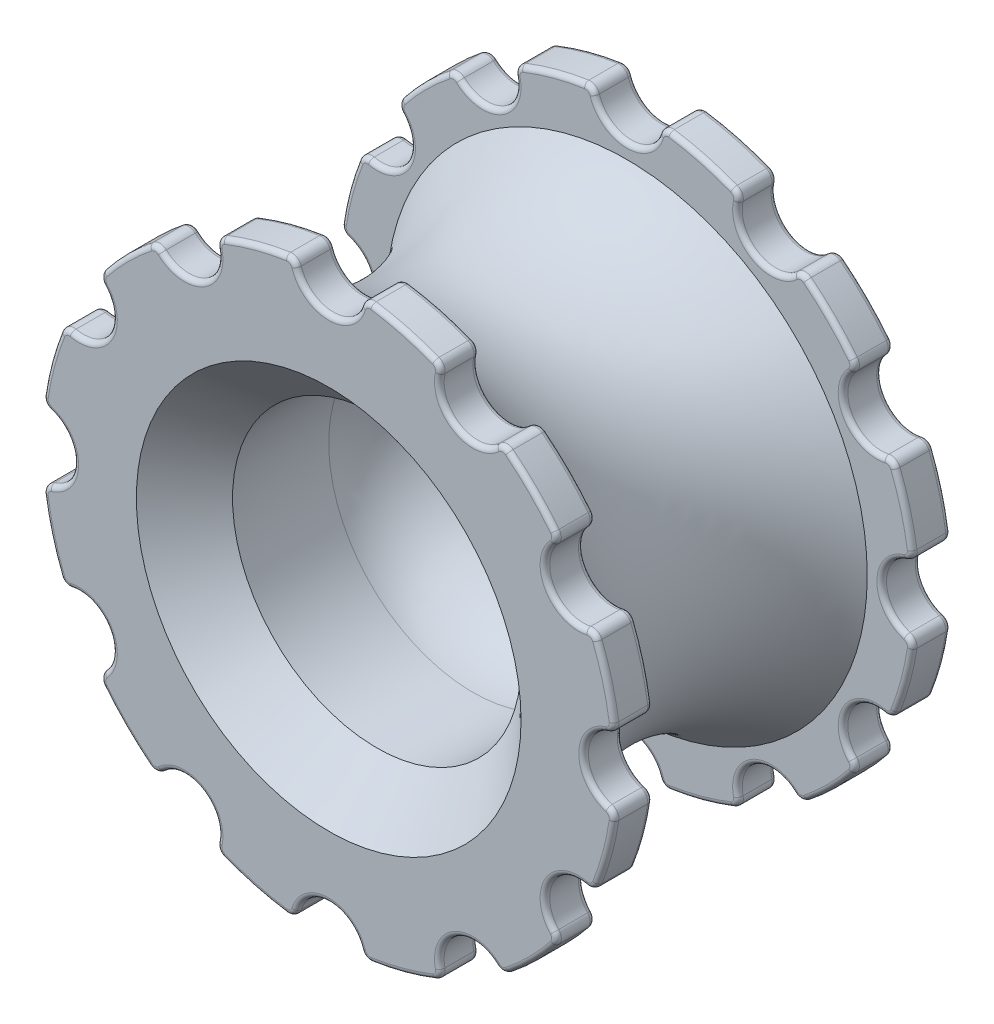
SolidWorks part; units mm, degrees
ref_plane "Спереди" through (0, 0, 0) normal (0, 0, 1) x (1, 0, 0)
ref_plane "Сверху" through (0, 0, 0) normal (0, 1, 0) x (1, 0, 0)
ref_plane "Справа" through (0, 0, 0) normal (1, 0, 0) x (0, 0, -1)
sketch "Эскиз1" plane through (0, 0, 0) normal (0, 0, 1) x (1, 0, 0)
  line L0 (0, -796.897) -> (0, 39047.9522) construction
  circle A0 centre (0, 0) radius 30 construction
  arc A1 (-3.494, 29.7958) -> (3.494, 29.7958) centre (0, 30) ccw
  arc A2 (3.494, 29.7958) -> (11.872, 27.551) centre (0, 0) cw
  arc A3 (11.872, 27.551) -> (17.9238, 24.0569) centre (15, 25.9808) ccw
  arc A4 (17.9238, 24.0569) -> (24.0569, 17.9238) centre (0, 0) cw
  arc A5 (24.0569, 17.9238) -> (27.551, 11.872) centre (25.9808, 15) ccw
  arc A6 (27.551, 11.872) -> (29.7958, 3.494) centre (0, 0) cw
  arc A7 (29.7958, 3.494) -> (29.7958, -3.494) centre (30, 0) ccw
  arc A8 (29.7958, -3.494) -> (27.551, -11.872) centre (0, 0) cw
  arc A9 (27.551, -11.872) -> (24.0569, -17.9238) centre (25.9808, -15) ccw
  arc A10 (24.0569, -17.9238) -> (17.9238, -24.0569) centre (0, 0) cw
  arc A11 (17.9238, -24.0569) -> (11.872, -27.551) centre (15, -25.9808) ccw
  arc A12 (11.872, -27.551) -> (3.494, -29.7958) centre (0, 0) cw
  arc A13 (3.494, -29.7958) -> (-3.494, -29.7958) centre (0, -30) ccw
  arc A14 (-3.494, -29.7958) -> (-11.872, -27.551) centre (0, 0) cw
  arc A15 (-11.872, -27.551) -> (-17.9238, -24.0569) centre (-15, -25.9808) ccw
  arc A16 (-17.9238, -24.0569) -> (-24.0569, -17.9238) centre (0, 0) cw
  arc A17 (-24.0569, -17.9238) -> (-27.551, -11.872) centre (-25.9808, -15) ccw
  arc A18 (-27.551, -11.872) -> (-29.7958, -3.494) centre (0, 0) cw
  arc A19 (-29.7958, -3.494) -> (-29.7958, 3.494) centre (-30, 0) ccw
  arc A20 (-29.7958, 3.494) -> (-27.551, 11.872) centre (0, 0) cw
  arc A21 (-27.551, 11.872) -> (-24.0569, 17.9238) centre (-25.9808, 15) ccw
  arc A22 (-24.0569, 17.9238) -> (-17.9238, 24.0569) centre (0, 0) cw
  arc A23 (-17.9238, 24.0569) -> (-11.872, 27.551) centre (-15, 25.9808) ccw
  arc A24 (-11.872, 27.551) -> (-3.494, 29.7958) centre (0, 0) cw
  point P55 (0, 0)
  dimension "D1" = 3.5
  dimension "D2" = 0
  dimension "D3" = 30
  dimension "D4" = 12
  dimension "D5" = 60
extrude "Бобышка-Вытянуть1" add sketch "Эскиз1" along normal blind 35
fillet "Скругление1" radius 1 24 edges at (3.494, 29.7958, 17.5) (11.872, 27.551, 17.5) (17.9238, 24.0569, 17.5) (29.7958, 3.494, 17.5) (27.551, 11.872, 17.5) (24.0569, 17.9238, 17.5) (29.7958, -3.494, 17.5) (27.551, -11.872, 17.5) (17.9238, -24.0569, 17.5) (24.0569, -17.9238, 17.5) (11.872, -27.551, 17.5) (-11.872, -27.551, 17.5) (3.494, -29.7958, 17.5) (-3.494, -29.7958, 17.5) (-17.9238, -24.0569, 17.5) (-24.0569, -17.9238, 17.5) (-27.551, -11.872, 17.5) (-29.7958, -3.494, 17.5) (-29.7958, 3.494, 17.5) (-27.551, 11.872, 17.5) (-24.0569, 17.9238, 17.5) (-17.9238, 24.0569, 17.5) (-11.872, 27.551, 17.5) (-3.494, 29.7958, 17.5)
sketch "Эскиз2" plane through (0, 0, 0) normal (0, 1, 0) x (1, 0, 0)
  line L0 (0, -1000) -> (0, 49000) construction
  line L2 (-30, -4) -> (-30, -31)
  line L5 (-30, -4) -> (-25, -4)
  line L6 (-30, -31) -> (-25, -31)
  arc A1 (-25, -4) -> (-25, -31) centre (-39.7564, -17.5) cw
  dimension "D3" = 5
  dimension "D5" = 20
  dimension "D1" = 4
  dimension "D2" = 27
  dimension "D4" = 30
revolve "Вырез-Повернуть1" cut sketch "Эскиз2" angle 360 about L0
sketch "Эскиз3" plane through (0, 0, 35) normal (0, 0, 1) x (1, 0, 0)
  circle A0 centre (0, 0) radius 15
  dimension "D1" = 30
extrude "Вырез-Вытянуть1" cut sketch "Эскиз3" against normal blind 25
fillet "Скругление2" radius 0.5 192 edges at (-29.5254, -3.7689, 4) (-26.5, 0, 4) (-29.5254, 3.7689, 4) (-28.9778, 7.7646, 4) (-27.4542, 11.4987, 4) (-22.9497, 13.25, 4) (-23.6853, 18.0266, 4) (-21.2132, 21.2132, 4) (-18.0266, 23.6853, 4) (-13.25, 22.9497, 4) (-11.4987, 27.4542, 4) (-7.7646, 28.9778, 4) (-3.7689, 29.5254, 4) (0, 26.5, 4) (3.7689, 29.5254, 4) (7.7646, 28.9778, 4) (11.4987, 27.4542, 4) (13.25, 22.9497, 4) (18.0266, 23.6853, 4) (21.2132, 21.2132, 4) (23.6853, 18.0266, 4) (22.9497, 13.25, 4) (27.4542, 11.4987, 4) (28.9778, 7.7646, 4) (29.5254, 3.7689, 4) (26.5, 0, 4) (29.5254, -3.7689, 4) (28.9778, -7.7646, 4) (27.4542, -11.4987, 4) (22.9497, -13.25, 4) (23.6853, -18.0266, 4) (21.2132, -21.2132, 4) (18.0266, -23.6853, 4) (13.25, -22.9497, 4) (11.4987, -27.4542, 4) (7.7646, -28.9778, 4) (3.7689, -29.5254, 4) (0, -26.5, 4) (-3.7689, -29.5254, 4) (-7.7646, -28.9778, 4) (-11.4987, -27.4542, 4) (-13.25, -22.9497, 4) (-18.0266, -23.6853, 4) (-21.2132, -21.2132, 4) (-23.6853, -18.0266, 4) (-22.9497, -13.25, 4) (-27.4542, -11.4987, 4) (-29.5254, -3.7689, 31) (-26.5, 0, 31) (-29.5254, 3.7689, 31) (-28.9778, 7.7646, 31) (-27.4542, 11.4987, 31) (-22.9497, 13.25, 31) (-23.6853, 18.0266, 31) (-21.2132, 21.2132, 31) (-18.0266, 23.6853, 31) (-13.25, 22.9497, 31) (-11.4987, 27.4542, 31) (-7.7646, 28.9778, 31) (-3.7689, 29.5254, 31) (0, 26.5, 31) (3.7689, 29.5254, 31) (7.7646, 28.9778, 31) (11.4987, 27.4542, 31) (13.25, 22.9497, 31) (18.0266, 23.6853, 31) (21.2132, 21.2132, 31) (23.6853, 18.0266, 31) (22.9497, 13.25, 31) (27.4542, 11.4987, 31) (28.9778, 7.7646, 31) (29.5254, 3.7689, 31) (26.5, 0, 31) (29.5254, -3.7689, 31) (28.9778, -7.7646, 31) (27.4542, -11.4987, 31) (22.9497, -13.25, 31) (23.6853, -18.0266, 31) (21.2132, -21.2132, 31) (18.0266, -23.6853, 31) (13.25, -22.9497, 31) (11.4987, -27.4542, 31) (7.7646, -28.9778, 31) (3.7689, -29.5254, 31) (0, -26.5, 31) (-3.7689, -29.5254, 31) (-7.7646, -28.9778, 31) (-11.4987, -27.4542, 31) (-13.25, -22.9497, 31) (-18.0266, -23.6853, 31) (-21.2132, -21.2132, 31) (-23.6853, -18.0266, 31) (-22.9497, -13.25, 31) (-27.4542, -11.4987, 31) (-29.5254, 3.7689, 35) (-28.9778, 7.7646, 35) (-27.4542, 11.4987, 35) (-22.9497, 13.25, 35) (-23.6853, 18.0266, 35) (-21.2132, 21.2132, 35) (-18.0266, 23.6853, 35) (-13.25, 22.9497, 35) (-11.4987, 27.4542, 35) (-7.7646, 28.9778, 35) (-3.7689, 29.5254, 35) (0, 26.5, 35) (3.7689, 29.5254, 35) (7.7646, 28.9778, 35) (11.4987, 27.4542, 35) (13.25, 22.9497, 35) (18.0266, 23.6853, 35) (21.2132, 21.2132, 35) (23.6853, 18.0266, 35) (22.9497, 13.25, 35) (27.4542, 11.4987, 35) (28.9778, 7.7646, 35) (29.5254, 3.7689, 35) (26.5, 0, 35) (29.5254, -3.7689, 35) (28.9778, -7.7646, 35) (27.4542, -11.4987, 35) (22.9497, -13.25, 35) (23.6853, -18.0266, 35) (21.2132, -21.2132, 35) (18.0266, -23.6853, 35) (13.25, -22.9497, 35) (11.4987, -27.4542, 35) (7.7646, -28.9778, 35) (3.7689, -29.5254, 35) (0, -26.5, 35) (-3.7689, -29.5254, 35) (-7.7646, -28.9778, 35) (-11.4987, -27.4542, 35) (-13.25, -22.9497, 35) (-18.0266, -23.6853, 35) (-21.2132, -21.2132, 35) (-23.6853, -18.0266, 35) (-22.9497, -13.25, 35) (-27.4542, -11.4987, 35) (-28.9778, -7.7646, 35) (-29.5254, -3.7689, 35) (3.7689, 29.5254, 0) (0, 26.5, 0) (-3.7689, 29.5254, 0) (-7.7646, 28.9778, 0) (-11.4987, 27.4542, 0) (-13.25, 22.9497, 0) (-18.0266, 23.6853, 0) (-21.2132, 21.2132, 0) (-23.6853, 18.0266, 0) (-22.9497, 13.25, 0) (-27.4542, 11.4987, 0) (-28.9778, 7.7646, 0) (-29.5254, 3.7689, 0) (-26.5, 0, 0) (-29.5254, -3.7689, 0) (-28.9778, -7.7646, 0) (-27.4542, -11.4987, 0) (-22.9497, -13.25, 0) (-23.6853, -18.0266, 0) (-21.2132, -21.2132, 0) (-18.0266, -23.6853, 0) (-13.25, -22.9497, 0) (-11.4987, -27.4542, 0) (-7.7646, -28.9778, 0) (-3.7689, -29.5254, 0) (0, -26.5, 0) (3.7689, -29.5254, 0) (7.7646, -28.9778, 0) (11.4987, -27.4542, 0) (13.25, -22.9497, 0) (18.0266, -23.6853, 0) (21.2132, -21.2132, 0) (23.6853, -18.0266, 0) (22.9497, -13.25, 0) (27.4542, -11.4987, 0) (28.9778, -7.7646, 0) (29.5254, -3.7689, 0) (26.5, 0, 0) (29.5254, 3.7689, 0) (28.9778, 7.7646, 0) (27.4542, 11.4987, 0) (22.9497, 13.25, 0) (23.6853, 18.0266, 0) (21.2132, 21.2132, 0) (18.0266, 23.6853, 0) (13.25, 22.9497, 0) (11.4987, 27.4542, 0) (7.7646, 28.9778, 0) (-28.9778, -7.7646, 4) (-28.9778, -7.7646, 31) (-26.5, 0, 35)
fillet "Скругление3" radius 10 1 edges at (15, 0, 10)
chamfer "Фаска1" distance 5 angle 45 1 edges at (15, 0, 35)
sketch "Эскиз4" plane through (0, 0, 0) normal (0, 0, -1) x (-1, 0, 0)
  circle A0 centre (0, 0) radius 6
  dimension "D1" = 12
extrude "Бобышка-Вытянуть2" add sketch "Эскиз4" along normal blind 1
sketch "Эскиз5" plane through (0, 0, -1) normal (0, 0, -1) x (-1, 0, 0)
  circle A0 centre (0, 0) radius 3.75
  dimension "D1" = 7.5
extrude "Бобышка-Вытянуть3" add sketch "Эскиз5" along normal blind 3.5
sketch "Эскиз6" plane through (0, 0, -4.5) normal (0, 0, -1) x (-1, 0, 0)
  circle A0 centre (0, 0) radius 2.7
  dimension "D1" = 5.4
extrude "Вырез-Вытянуть2" cut sketch "Эскиз6" against normal blind 1
sketch "Эскиз7" plane through (0, 0, -3.5) normal (0, 0, -1) x (-1, 0, 0)
  line L0 (-1.85, 1.9666) -> (-1.85, -1.9666)
  line L2 (1.85, 1.9666) -> (1.85, -1.9666)
  arc A0 (-1.85, -1.9666) -> (1.85, -1.9666) centre (0, 0) ccw
  circle A1 centre (0, 0) radius 2.7 construction
  arc A2 (1.85, 1.9666) -> (-1.85, 1.9666) centre (0, 0) ccw
  dimension "D1" = 3.7
extrude "Вырез-Вытянуть3" cut sketch "Эскиз7" against normal blind 8
sketch "Эскиз8" plane through (0, 0, 10) normal (0, 0, 1) x (1, 0, 0)
  circle A0 centre (0, 0) radius 1.475
  dimension "D1" = 2.95
extrude "Вырез-Вытянуть4" cut sketch "Эскиз8" against normal blind 17
